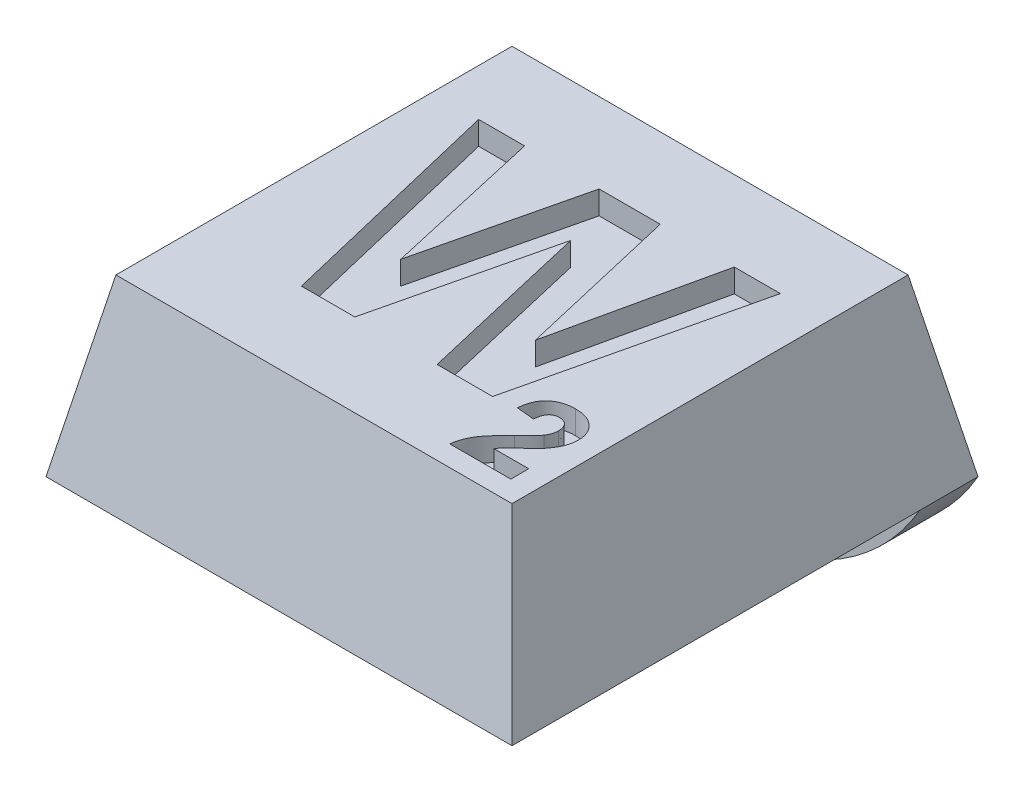
SolidWorks part; units mm, degrees
ref_plane "Front Plane" through (0, 0, 0) normal (0, 0, 1) x (1, 0, 0)
ref_plane "Top Plane" through (0, 0, 0) normal (0, 1, 0) x (1, 0, 0)
ref_plane "Right Plane" through (0, 0, 0) normal (1, 0, 0) x (0, 0, -1)
sketch "Sketch1" plane through (0, 0, 0) normal (0, 1, 0) x (1, 0, 0)
  line L1 (0, 0) -> (8, 0)
  line L2 (0, 0) -> (0, 8)
  line L3 (0, 8) -> (8, 8)
  line L4 (8, 0) -> (8, 8)
  dimension "D1" = 8
  dimension "D2" = 8
extrude "Boss-Extrude1" add sketch "Sketch1" along normal blind 3
sketch "Sketch2" plane through (0, 0, 0) normal (0, 0, 1) x (1, 0, 0)
  line L0 (0, 0) -> (0.6, 3)
  line L1 (0, 3) -> (8, 3) construction
  line L2 (0.6, 3) -> (0, 3)
  line L3 (0, 3) -> (0, 0)
  line L4 (8, 0) -> (7.4, 3)
  line L5 (7.4, 3) -> (8, 3)
  line L6 (8, 3) -> (8, 0)
  dimension "D1" = 0.6
  dimension "D2" = 0.6
extrude "Cut-Extrude1" cut sketch "Sketch2" against normal through all both and the other way through all
sketch "Sketch3" plane through (0, 0, 0) normal (1, 0, 0) x (0, 0, -1)
  line L0 (0, 0) -> (0.6, 3)
  line L1 (8, 3) -> (0, 3) construction
  line L2 (0.6, 3) -> (0, 3)
  line L3 (0, 3) -> (0, 0)
  line L4 (8, 3) -> (7.4, 3)
  line L5 (7.4, 3) -> (8, 0)
  line L6 (8, 3) -> (8, 0)
  dimension "D1" = 0.6
  dimension "D2" = 0.6
extrude "Cut-Extrude2" cut sketch "Sketch3" along normal blind 11
sketch "Sketch4" plane through (0, 0, 0) normal (0, -1, 0) x (1, 0, 0)
  line L0 (8, 0) -> (8, -8) construction
  line L3 (0, 0) -> (8, 0) construction
  circle A0 centre (4, -3.75) radius 1.8
  dimension "D1" = 3.6
  dimension "D2" = 4
  dimension "D3" = 3.75
extrude "Cut-Extrude3" cut sketch "Sketch4" against normal blind 0.8
sketch "Sketch5" plane through (0, 0, 0) normal (0, -1, 0) x (1, 0, 0)
  line L0 (8, 0) -> (8, -8) construction
  line L1 (0, -8) -> (8, -8)
  line L2 (0, -8) -> (0, -7)
  line L3 (0, -7) -> (8, -7)
  line L4 (8, -8) -> (8, -7)
  dimension "D1" = 1
extrude "Boss-Extrude2" add sketch "Sketch5" along normal blind 2
fillet "Fillet1" radius 4 2 edges at (8, -2, -7.5) (0, -2, -7.5)
sketch "Sketch6" plane through (0, 3, 0) normal (0, 1, 0) x (1, 0, 0)
  text T0 "W" font "Arial" height 4
extrude "Cut-Extrude4" cut sketch "Sketch6" against normal blind 0.4
sketch "Sketch7" plane through (0, 3, 0) normal (0, 1, 0) x (1, 0, 0)
  text T0 "2" font "Arial" height 1.6
extrude "Cut-Extrude5" cut sketch "Sketch7" against normal blind 0.4
